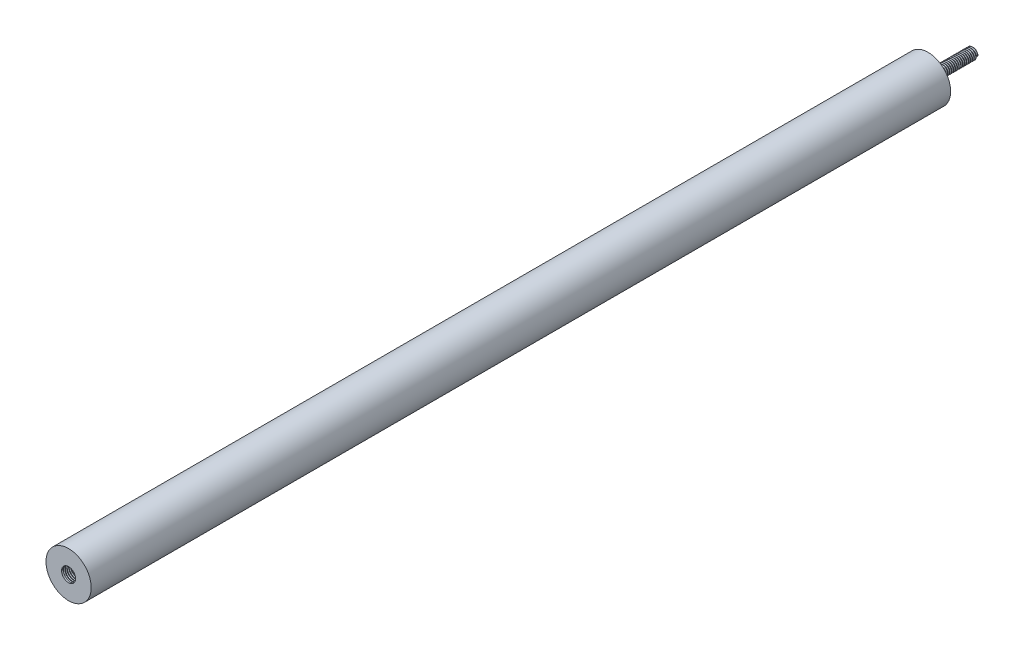
SolidWorks part; units mm, degrees
ref_plane "Front Plane" through (0, 0, 0) normal (0, 0, 1) x (1, 0, 0)
ref_plane "Top Plane" through (0, 0, 0) normal (0, 1, 0) x (1, 0, 0)
ref_plane "Right Plane" through (0, 0, 0) normal (1, 0, 0) x (0, 0, -1)
sketch "Sketch1" plane through (0, 0, 0) normal (0, 0, 1) x (1, 0, 0)
  line L1 (0, 0) -> (25.4, 0)
  line L2 (0, 0) -> (0, 32.766)
  line L3 (0, 32.766) -> (25.4, 32.766)
  line L4 (25.4, 0) -> (25.4, 32.766)
  dimension "D1" = 25.4
  dimension "D2" = 32.766
extrude "Boss-Extrude1" add sketch "Sketch1" against normal blind 482.6
sketch "Sketch2" plane through (0, 0, 0) normal (0, 0, 1) x (1, 0, 0)
  line L0 (25.4, 32.766) -> (0, 32.766) construction
  line L1 (25.4, 0) -> (25.4, 32.766) construction
  line L3 (0, 32.766) -> (25.4, 32.766)
  line L4 (0, 32.766) -> (0, 0)
  line L5 (0, 0) -> (25.4, 0)
  line L6 (25.4, 32.766) -> (25.4, 0)
  circle A0 centre (12.7, 16.383) radius 12.7
  line M2 (0, 32.766) -> (0, 0)
  line M3 (0, 0) -> (25.4, 0)
  line M4 (25.4, 0) -> (25.4, 32.766)
  line M5 (25.4, 32.766) -> (0, 32.766)
  dimension "D1" = 25.4
  dimension "D2" = 16.383
  dimension "D3" = 12.7
extrude "Cut-Extrude1" cut sketch "Sketch2" against normal through all contours A0 L6 M5 M2 | A0 L4 M3 M4 region at (12.7, 32.4637, 0) region at (12.7, 3.3807, 0)
sketch "Sketch3" plane through (0, 0, 0) normal (0, 0, 1) x (1, 0, 0)
  circle A0 centre (12.7, 16.383) radius 3.937
  dimension "D1" = 7.874
extrude "Cut-Extrude2" cut sketch "Sketch3" against normal blind 12.7
thread "Thread1" pitch 1.0583 method cut profile "Thread Profile1" start angle 0, offset 0, length 0, pitch 1.0583, diameter 7.874
ref_plane "Plane1" through (8.763, 16.383, 0) normal (0, -1, 0) x (-1, 0, 0)
sketch "Thread Profile1" plane through (8.763, 16.383, 0) normal (0, -1, 0) x (-1, 0, 0)
  line L0 (0, 0) -> (0, 1.0583) construction
  line L1 (0, 0) -> (0.5728, 0.3307)
  line L2 (0.5728, 0.3307) -> (0.5728, 0.463)
  line L3 (0.5728, 0.463) -> (0, 0.7937)
  line L4 (0.5728, 0.3969) -> (0, 0.3969) construction
  line L11 (0, 0) -> (0, 0.7937)
  point P2 (0, 0)
  dimension "Pitch" = 1.0583
  dimension "Profile_Angle" = 60
  dimension "Profile_Land" = 0.1323
  dimension "Profile_Height" = 0.5728
sketch "Sketch4" plane through (0, 0, -482.6) normal (0, 0, -1) x (-1, 0, 0)
  circle A0 centre (-12.7, 16.383) radius 2.413
  dimension "D1" = 4.826
extrude "Boss-Extrude2" add sketch "Sketch4" along normal blind 25.4
thread "Thread2" pitch 1.0583 method extrude profile "Thread Profile2" start angle 0, offset 0, length 0, pitch 1.0583, diameter 4.826
ref_plane "Plane2" through (15.113, 16.383, -508) normal (0, -1, 0) x (1, 0, 0)
sketch "Thread Profile2" plane through (15.113, 16.383, -508) normal (0, -1, 0) x (1, 0, 0)
  line L0 (0, 0) -> (0, 1.0583) construction
  line L1 (0, 0) -> (0.5728, 0.3307)
  line L2 (0.5728, 0.3307) -> (0.5728, 0.463)
  line L3 (0.5728, 0.463) -> (0, 0.7937)
  line L4 (0.5728, 0.3969) -> (0, 0.3969) construction
  line L11 (0, 0) -> (0, 0.7937)
  point P2 (0, 0)
  dimension "Pitch" = 1.0583
  dimension "Profile_Angle" = 60
  dimension "Profile_Land" = 0.1323
  dimension "Profile_Height" = 0.5728
